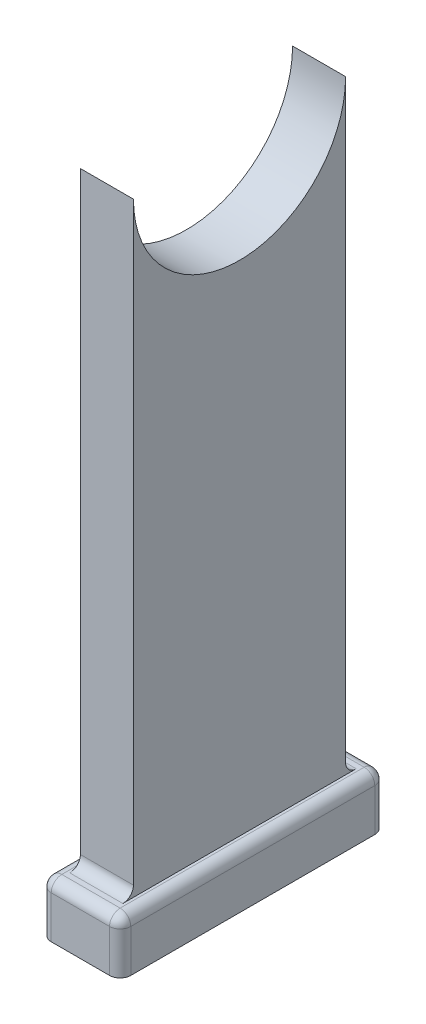
SolidWorks part; units mm, degrees
ref_plane "정면" through (0, 0, 0) normal (0, 0, 1) x (1, 0, 0)
ref_plane "윗면" through (0, 0, 0) normal (0, 1, 0) x (1, 0, 0)
ref_plane "우측면" through (0, 0, 0) normal (1, 0, 0) x (0, 0, -1)
sketch "스케치1" plane through (0, 0, 0) normal (0, 1, 0) x (1, 0, 0)
  line L0 (-48.4348, 0) -> (48.5217, 0) construction
  line L1 (0, 41.6522) -> (0, -39.5652) construction
  line L3 (7.5, -25) -> (-7.5, -25)
  line L4 (7.5, -25) -> (7.5, 25)
  line L5 (7.5, 25) -> (-7.5, 25)
  line L6 (-7.5, -25) -> (-7.5, 25)
  line L7 (7.5, -25) -> (-7.5, 25) construction
  line L8 (7.5, 25) -> (-7.5, -25) construction
  point P5 (0, 0)
  dimension "D1" = 50
  dimension "D2" = 15
extrude "보스-돌출1" add sketch "스케치1" along normal blind 10
fillet "필렛1" radius 2 4 edges at (7.5, 10, 0) (0, 10, 25) (-7.5, 10, 0) (0, 10, -25)
fillet "필렛2" radius 2 8 edges at (-6.9142, 9.4142, -24.4142) (6.9142, 9.4142, -24.4142) (6.9142, 9.4142, 24.4142) (-6.9142, 9.4142, 24.4142) (-7.5, 4, -25) (7.5, 4, -25) (7.5, 4, 25) (-7.5, 4, 25)
sketch "스케치4" plane through (0, 0, 0) normal (1, 0, 0) x (0, 0, -1)
  line L0 (-23, 0) -> (23, 0) construction
  line L1 (20, 0) -> (-20, 0)
  line L2 (20, 0) -> (20, 104)
  line L4 (-20, 0) -> (-20, 104)
  line L5 (-23, 8) -> (-23, 0) construction
  line L6 (23, 0) -> (23, 8) construction
  line L7 (20, 124) -> (20, 104)
  line L8 (-20, 124) -> (-20, 104)
  arc A0 (-20, 124) -> (20, 124) centre (0, 124) ccw
  dimension "D1" = 3
  dimension "D2" = 3
extrude "보스-돌출3" add sketch "스케치4" along normal mid plane 10
fillet "필렛3" radius 2 2 edges at (0, 10, -20) (0, 10, 20)
equation "\"10.00mma2\"=10"
